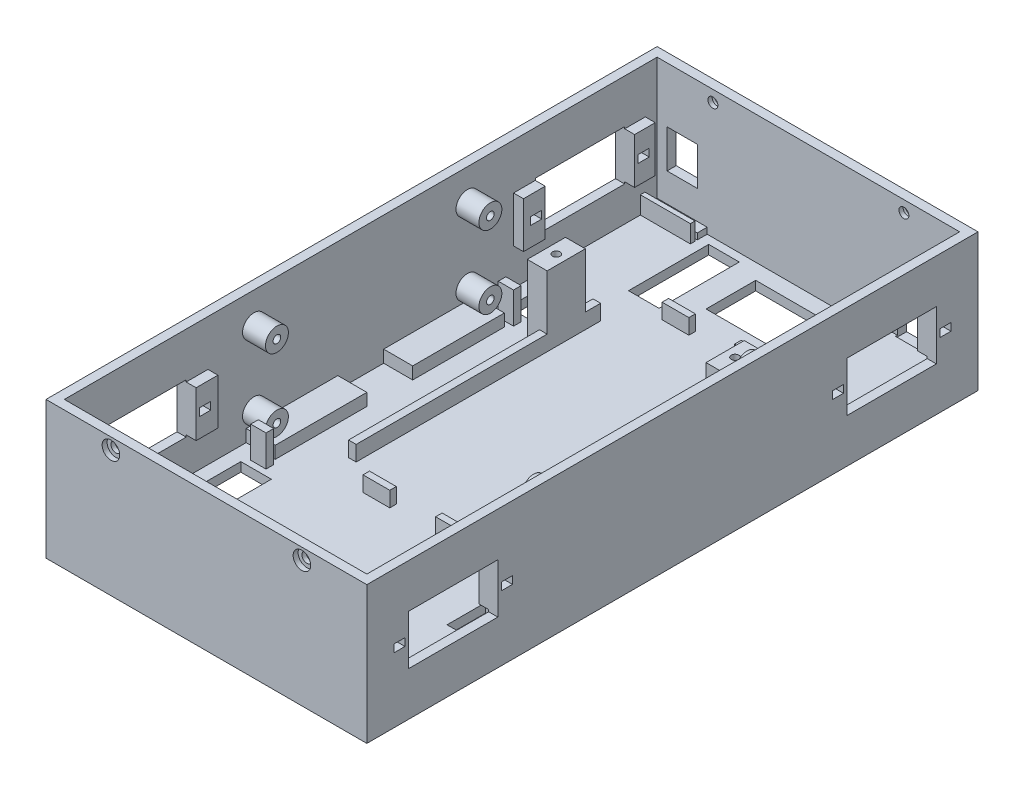
SolidWorks part; units mm, degrees
ref_plane "Front Plane" through (0, 0, 0) normal (0, 0, 1) x (1, 0, 0)
ref_plane "Top Plane" through (0, 0, 0) normal (0, 1, 0) x (1, 0, 0)
ref_plane "Right Plane" through (0, 0, 0) normal (1, 0, 0) x (0, 0, -1)
sketch "Sketch1" plane through (0, 0, 0) normal (0, 0, 1) x (1, 0, 0)
  line L1 (-42, 0) -> (42, 0)
  line L2 (-42, 0) -> (-42, 36)
  line L3 (-42, 36) -> (42, 36)
  line L4 (42, 0) -> (42, 36)
extrude "Boss-Extrude1" add sketch "Sketch1" along normal blind 160 from offset 80 offset against normal yes
sketch "Sketch2" plane through (0, 0, 0) normal (0, 0, 1) x (1, 0, 0)
  line L1 (-39.6, 2.4) -> (39.6, 2.4)
  line L2 (-39.6, 2.4) -> (-39.6, 41)
  line L3 (-39.6, 41) -> (39.6, 41)
  line L4 (39.6, 2.4) -> (39.6, 41)
extrude "Boss-Extrude2" add sketch "Sketch2" along normal blind 155.2 from offset 77.6 separate body offset against normal yes
combine bodies "Combine1" operation type subtract main body 101 bodies to subtract 102
sketch "Sketch3" plane through (0, 0, 0) normal (0, 0, 1) x (1, 0, 0)
  line L1 (-39.6, 12) -> (-37, 12)
  line L2 (-39.6, 12) -> (-39.6, 24)
  line L3 (-39.6, 24) -> (-37, 24)
  line L4 (-37, 12) -> (-37, 24)
extrude "Boss-Extrude3" add sketch "Sketch3" along normal blind 34.5 from offset 74.5 offset against normal yes
sketch "Sketch4" plane through (0, 0, 0) normal (0, 0, 1) x (1, 0, 0)
  line L1 (-43, 11.5) -> (-35.2, 11.5)
  line L2 (-43, 11.5) -> (-43, 24.5)
  line L3 (-43, 24.5) -> (-35.2, 24.5)
  line L4 (-35.2, 11.5) -> (-35.2, 24.5)
extrude "Boss-Extrude4" add sketch "Sketch4" along normal blind 23.4 from offset 69.1 separate body offset against normal yes
combine bodies "Combine2" operation type subtract main body 104 bodies to subtract 105
sketch "Sketch5" plane through (0, 0, 0) normal (0, 0, 1) x (1, 0, 0)
  line L1 (-43, 17) -> (-35.2, 17)
  line L2 (-43, 17) -> (-43, 19)
  line L3 (-43, 19) -> (-35.2, 19)
  line L4 (-35.2, 17) -> (-35.2, 19)
extrude "Boss-Extrude5" add sketch "Sketch5" along normal blind 2.9 from offset 72.925 separate body offset against normal yes
combine bodies "Combine3" operation type subtract main body 106 bodies to subtract 107
sketch "Sketch6" plane through (0, 0, 0) normal (0, 0, 1) x (1, 0, 0)
  line L1 (-43, 17) -> (-35.2, 17)
  line L2 (-43, 17) -> (-43, 19)
  line L3 (-43, 19) -> (-35.2, 19)
  line L4 (-35.2, 17) -> (-35.2, 19)
extrude "Boss-Extrude6" add sketch "Sketch6" along normal blind 2.9 from offset 44.775 separate body offset against normal yes
combine bodies "Combine4" operation type subtract main body 108 bodies to subtract 109
sketch "Sketch7" plane through (0, 0, 0) normal (0, 0, 1) x (1, 0, 0)
  line L1 (-36, -1) -> (-28, -1)
  line L2 (-36, -1) -> (-36, 3.4)
  line L3 (-36, 3.4) -> (-28, 3.4)
  line L4 (-28, -1) -> (-28, 3.4)
extrude "Boss-Extrude7" add sketch "Sketch7" along normal blind 10 from offset 45 separate body offset against normal yes
combine bodies "Combine5" operation type subtract main body 110 bodies to subtract 111
sketch "Sketch8" plane through (0, 0, 0) normal (0, 0, 1) x (1, 0, 0)
  line L1 (-39.6, 12) -> (-37, 12)
  line L2 (-39.6, 12) -> (-39.6, 24)
  line L3 (-39.6, 24) -> (-37, 24)
  line L4 (-37, 12) -> (-37, 24)
extrude "Boss-Extrude8" add sketch "Sketch8" along normal blind 34.5 from offset 40
sketch "Sketch9" plane through (0, 0, 0) normal (0, 0, 1) x (1, 0, 0)
  line L1 (-43, 11.5) -> (-35.2, 11.5)
  line L2 (-43, 11.5) -> (-43, 24.5)
  line L3 (-43, 24.5) -> (-35.2, 24.5)
  line L4 (-35.2, 11.5) -> (-35.2, 24.5)
extrude "Boss-Extrude9" add sketch "Sketch9" along normal blind 23.4 from offset 45.7 separate body
combine bodies "Combine6" operation type subtract main body 113 bodies to subtract 114
sketch "Sketch10" plane through (0, 0, 0) normal (0, 0, 1) x (1, 0, 0)
  line L1 (-43, 17) -> (-35.2, 17)
  line L2 (-43, 17) -> (-43, 19)
  line L3 (-43, 19) -> (-35.2, 19)
  line L4 (-35.2, 17) -> (-35.2, 19)
extrude "Boss-Extrude10" add sketch "Sketch10" along normal blind 2.9 from offset 41.875 separate body
combine bodies "Combine7" operation type subtract main body 115 bodies to subtract 116
sketch "Sketch11" plane through (0, 0, 0) normal (0, 0, 1) x (1, 0, 0)
  line L1 (-43, 17) -> (-35.2, 17)
  line L2 (-43, 17) -> (-43, 19)
  line L3 (-43, 19) -> (-35.2, 19)
  line L4 (-35.2, 17) -> (-35.2, 19)
extrude "Boss-Extrude11" add sketch "Sketch11" along normal blind 2.9 from offset 70.025 separate body
combine bodies "Combine8" operation type subtract main body 117 bodies to subtract 118
sketch "Sketch12" plane through (0, 0, 0) normal (0, 0, 1) x (1, 0, 0)
  line L1 (-36, -1) -> (-28, -1)
  line L2 (-36, -1) -> (-36, 3.4)
  line L3 (-36, 3.4) -> (-28, 3.4)
  line L4 (-28, -1) -> (-28, 3.4)
extrude "Boss-Extrude12" add sketch "Sketch12" along normal blind 10 from offset 35 separate body
combine bodies "Combine9" operation type subtract main body 119 bodies to subtract 120
sketch "Sketch13" plane through (0, 0, 0) normal (1, 0, 0) x (0, 0, -1)
  circle A0 centre (27.94, 8.775) radius 3
extrude "Boss-Extrude13" add sketch "Sketch13" along normal blind 6 from offset 39.6 offset against normal yes
sketch "Sketch14" plane through (0, 0, 0) normal (1, 0, 0) x (0, 0, -1)
  circle A0 centre (27.94, 8.775) radius 1
extrude "Boss-Extrude14" add sketch "Sketch14" along normal blind 7.4 from offset 40.4 separate body offset against normal yes
combine bodies "Combine10" operation type subtract main body 122 bodies to subtract 123
sketch "Sketch15" plane through (0, 0, 0) normal (1, 0, 0) x (0, 0, -1)
  circle A0 centre (27.94, 27.825) radius 3
extrude "Boss-Extrude15" add sketch "Sketch15" along normal blind 6 from offset 39.6 offset against normal yes
sketch "Sketch16" plane through (0, 0, 0) normal (1, 0, 0) x (0, 0, -1)
  circle A0 centre (27.94, 27.825) radius 1
extrude "Boss-Extrude16" add sketch "Sketch16" along normal blind 7.4 from offset 40.4 separate body offset against normal yes
combine bodies "Combine11" operation type subtract main body 125 bodies to subtract 126
sketch "Sketch17" plane through (0, 0, 0) normal (1, 0, 0) x (0, 0, -1)
  circle A0 centre (-27.94, 8.775) radius 3
extrude "Boss-Extrude17" add sketch "Sketch17" along normal blind 6 from offset 39.6 offset against normal yes
sketch "Sketch18" plane through (0, 0, 0) normal (1, 0, 0) x (0, 0, -1)
  circle A0 centre (-27.94, 8.775) radius 1
extrude "Boss-Extrude18" add sketch "Sketch18" along normal blind 7.4 from offset 40.4 separate body offset against normal yes
combine bodies "Combine12" operation type subtract main body 128 bodies to subtract 129
sketch "Sketch19" plane through (0, 0, 0) normal (1, 0, 0) x (0, 0, -1)
  circle A0 centre (-27.94, 27.825) radius 3
extrude "Boss-Extrude19" add sketch "Sketch19" along normal blind 6 from offset 39.6 offset against normal yes
sketch "Sketch20" plane through (0, 0, 0) normal (1, 0, 0) x (0, 0, -1)
  circle A0 centre (-27.94, 27.825) radius 1
extrude "Boss-Extrude20" add sketch "Sketch20" along normal blind 7.4 from offset 40.4 separate body offset against normal yes
combine bodies "Combine13" operation type subtract main body 131 bodies to subtract 132
sketch "Sketch21" plane through (0, 0, 0) normal (0, 0, 1) x (1, 0, 0)
  line L1 (-39.6, 2.4) -> (-32, 2.4)
  line L2 (-39.6, 2.4) -> (-39.6, 5.6)
  line L3 (-39.6, 5.6) -> (-32, 5.6)
  line L4 (-32, 2.4) -> (-32, 5.6)
extrude "Boss-Extrude21" add sketch "Sketch21" along normal blind 24 from offset 30 offset against normal yes
sketch "Sketch22" plane through (0, 0, 0) normal (0, 0, 1) x (1, 0, 0)
  line L1 (-39.6, 2.4) -> (-32, 2.4)
  line L2 (-39.6, 2.4) -> (-39.6, 5.6)
  line L3 (-39.6, 5.6) -> (-32, 5.6)
  line L4 (-32, 2.4) -> (-32, 5.6)
extrude "Boss-Extrude22" add sketch "Sketch22" along normal blind 24 from offset 6
sketch "Sketch23" plane through (0, 0, 0) normal (0, 0, 1) x (1, 0, 0)
  line L1 (-35, 2.4) -> (-31, 2.4)
  line L2 (-35, 2.4) -> (-35, 10.6)
  line L3 (-35, 10.6) -> (-31, 10.6)
  line L4 (-31, 2.4) -> (-31, 10.6)
extrude "Boss-Extrude23" add sketch "Sketch23" along normal blind 2 from offset 31.4
sketch "Sketch24" plane through (0, 0, 0) normal (0, 0, 1) x (1, 0, 0)
  line L1 (-35, 2.4) -> (-31, 2.4)
  line L2 (-35, 2.4) -> (-35, 10.6)
  line L3 (-35, 10.6) -> (-31, 10.6)
  line L4 (-31, 2.4) -> (-31, 10.6)
extrude "Boss-Extrude24" add sketch "Sketch24" along normal blind 2 from offset 33.4 offset against normal yes
sketch "Sketch25" plane through (0, 0, 0) normal (0, 0, 1) x (1, 0, 0)
  line L1 (-22.8, 2.4) -> (-20.8, 2.4)
  line L2 (-22.8, 2.4) -> (-22.8, 6.4)
  line L3 (-22.8, 6.4) -> (-20.8, 6.4)
  line L4 (-20.8, 2.4) -> (-20.8, 6.4)
extrude "Boss-Extrude25" add sketch "Sketch25" along normal blind 64 from offset 44 offset against normal yes
sketch "Sketch26" plane through (0, 0, 0) normal (0, 0, 1) x (1, 0, 0)
  line L1 (-26, 2.4) -> (-20.8, 2.4)
  line L2 (-26, 2.4) -> (-26, 20.75)
  line L3 (-26, 20.75) -> (-20.8, 20.75)
  line L4 (-20.8, 2.4) -> (-20.8, 20.75)
extrude "Boss-Extrude26" add sketch "Sketch26" along normal blind 10 from offset 40 offset against normal yes
sketch "Sketch27" plane through (0, 0, 0) normal (0, 1, 0) x (1, 0, 0)
  circle A0 centre (-23.4, 35) radius 1
extrude "Boss-Extrude27" add sketch "Sketch27" along normal blind 13.75 from offset 8 separate body
combine bodies "Combine14" operation type subtract main body 139 bodies to subtract 140
sketch "Sketch28" plane through (0, 0, 0) normal (0, 0, 1) x (1, 0, 0)
  line L1 (-24, -1) -> (-16, -1)
  line L2 (-24, -1) -> (-24, 3.4)
  line L3 (-24, 3.4) -> (-16, 3.4)
  line L4 (-16, -1) -> (-16, 3.4)
extrude "Boss-Extrude28" add sketch "Sketch28" along normal blind 21 from offset 54.5 separate body
combine bodies "Combine15" operation type subtract main body 141 bodies to subtract 142
sketch "Sketch29" plane through (0, 0, 0) normal (0, 0, 1) x (1, 0, 0)
  line L1 (37, 12) -> (39.6, 12)
  line L2 (37, 12) -> (37, 24)
  line L3 (37, 24) -> (39.6, 24)
  line L4 (39.6, 12) -> (39.6, 24)
extrude "Boss-Extrude29" add sketch "Sketch29" along normal blind 34.5 from offset 74.5 offset against normal yes
sketch "Sketch30" plane through (0, 0, 0) normal (0, 0, 1) x (1, 0, 0)
  line L1 (35.2, 11.5) -> (43, 11.5)
  line L2 (35.2, 11.5) -> (35.2, 24.5)
  line L3 (35.2, 24.5) -> (43, 24.5)
  line L4 (43, 11.5) -> (43, 24.5)
extrude "Boss-Extrude30" add sketch "Sketch30" along normal blind 23.4 from offset 69.1 separate body offset against normal yes
combine bodies "Combine16" operation type subtract main body 144 bodies to subtract 145
sketch "Sketch31" plane through (0, 0, 0) normal (0, 0, 1) x (1, 0, 0)
  line L1 (35.2, 17) -> (43, 17)
  line L2 (35.2, 17) -> (35.2, 19)
  line L3 (35.2, 19) -> (43, 19)
  line L4 (43, 17) -> (43, 19)
extrude "Boss-Extrude31" add sketch "Sketch31" along normal blind 2.9 from offset 72.925 separate body offset against normal yes
combine bodies "Combine17" operation type subtract main body 146 bodies to subtract 147
sketch "Sketch32" plane through (0, 0, 0) normal (0, 0, 1) x (1, 0, 0)
  line L1 (35.2, 17) -> (43, 17)
  line L2 (35.2, 17) -> (35.2, 19)
  line L3 (35.2, 19) -> (43, 19)
  line L4 (43, 17) -> (43, 19)
extrude "Boss-Extrude32" add sketch "Sketch32" along normal blind 2.9 from offset 44.775 separate body offset against normal yes
combine bodies "Combine18" operation type subtract main body 148 bodies to subtract 149
sketch "Sketch33" plane through (0, 0, 0) normal (0, 0, 1) x (1, 0, 0)
  line L1 (28, -1) -> (36, -1)
  line L2 (28, -1) -> (28, 3.4)
  line L3 (28, 3.4) -> (36, 3.4)
  line L4 (36, -1) -> (36, 3.4)
extrude "Boss-Extrude33" add sketch "Sketch33" along normal blind 10 from offset 45 separate body offset against normal yes
combine bodies "Combine19" operation type subtract main body 150 bodies to subtract 151
sketch "Sketch34" plane through (0, 0, 0) normal (0, 0, 1) x (1, 0, 0)
  line L1 (37, 12) -> (39.6, 12)
  line L2 (37, 12) -> (37, 24)
  line L3 (37, 24) -> (39.6, 24)
  line L4 (39.6, 12) -> (39.6, 24)
extrude "Boss-Extrude34" add sketch "Sketch34" along normal blind 34.5 from offset 40
sketch "Sketch35" plane through (0, 0, 0) normal (0, 0, 1) x (1, 0, 0)
  line L1 (35.2, 11.5) -> (43, 11.5)
  line L2 (35.2, 11.5) -> (35.2, 24.5)
  line L3 (35.2, 24.5) -> (43, 24.5)
  line L4 (43, 11.5) -> (43, 24.5)
extrude "Boss-Extrude35" add sketch "Sketch35" along normal blind 23.4 from offset 45.7 separate body
combine bodies "Combine20" operation type subtract main body 153 bodies to subtract 154
sketch "Sketch36" plane through (0, 0, 0) normal (0, 0, 1) x (1, 0, 0)
  line L1 (35.2, 17) -> (43, 17)
  line L2 (35.2, 17) -> (35.2, 19)
  line L3 (35.2, 19) -> (43, 19)
  line L4 (43, 17) -> (43, 19)
extrude "Boss-Extrude36" add sketch "Sketch36" along normal blind 2.9 from offset 41.875 separate body
combine bodies "Combine21" operation type subtract main body 155 bodies to subtract 156
sketch "Sketch37" plane through (0, 0, 0) normal (0, 0, 1) x (1, 0, 0)
  line L1 (35.2, 17) -> (43, 17)
  line L2 (35.2, 17) -> (35.2, 19)
  line L3 (35.2, 19) -> (43, 19)
  line L4 (43, 17) -> (43, 19)
extrude "Boss-Extrude37" add sketch "Sketch37" along normal blind 2.9 from offset 70.025 separate body
combine bodies "Combine22" operation type subtract main body 157 bodies to subtract 158
sketch "Sketch38" plane through (0, 0, 0) normal (0, 0, 1) x (1, 0, 0)
  line L1 (28, -1) -> (36, -1)
  line L2 (28, -1) -> (28, 3.4)
  line L3 (28, 3.4) -> (36, 3.4)
  line L4 (36, -1) -> (36, 3.4)
extrude "Boss-Extrude38" add sketch "Sketch38" along normal blind 10 from offset 35 separate body
combine bodies "Combine23" operation type subtract main body 159 bodies to subtract 160
sketch "Sketch39" plane through (0, 0, 0) normal (1, 0, 0) x (0, 0, -1)
  circle A0 centre (27.94, 8.775) radius 3
extrude "Boss-Extrude39" add sketch "Sketch39" along normal blind 6 from offset 33.6
sketch "Sketch40" plane through (0, 0, 0) normal (1, 0, 0) x (0, 0, -1)
  circle A0 centre (27.94, 8.775) radius 1
extrude "Boss-Extrude40" add sketch "Sketch40" along normal blind 7.4 from offset 33 separate body
combine bodies "Combine24" operation type subtract main body 162 bodies to subtract 163
sketch "Sketch41" plane through (0, 0, 0) normal (1, 0, 0) x (0, 0, -1)
  circle A0 centre (27.94, 27.825) radius 3
extrude "Boss-Extrude41" add sketch "Sketch41" along normal blind 6 from offset 33.6
sketch "Sketch42" plane through (0, 0, 0) normal (1, 0, 0) x (0, 0, -1)
  circle A0 centre (27.94, 27.825) radius 1
extrude "Boss-Extrude42" add sketch "Sketch42" along normal blind 7.4 from offset 33 separate body
combine bodies "Combine25" operation type subtract main body 165 bodies to subtract 166
sketch "Sketch43" plane through (0, 0, 0) normal (1, 0, 0) x (0, 0, -1)
  circle A0 centre (-27.94, 8.775) radius 3
extrude "Boss-Extrude43" add sketch "Sketch43" along normal blind 6 from offset 33.6
sketch "Sketch44" plane through (0, 0, 0) normal (1, 0, 0) x (0, 0, -1)
  circle A0 centre (-27.94, 8.775) radius 1
extrude "Boss-Extrude44" add sketch "Sketch44" along normal blind 7.4 from offset 33 separate body
combine bodies "Combine26" operation type subtract main body 168 bodies to subtract 169
sketch "Sketch45" plane through (0, 0, 0) normal (1, 0, 0) x (0, 0, -1)
  circle A0 centre (-27.94, 27.825) radius 3
extrude "Boss-Extrude45" add sketch "Sketch45" along normal blind 6 from offset 33.6
sketch "Sketch46" plane through (0, 0, 0) normal (1, 0, 0) x (0, 0, -1)
  circle A0 centre (-27.94, 27.825) radius 1
extrude "Boss-Extrude46" add sketch "Sketch46" along normal blind 7.4 from offset 33 separate body
combine bodies "Combine27" operation type subtract main body 171 bodies to subtract 172
sketch "Sketch47" plane through (0, 0, 0) normal (0, 0, 1) x (1, 0, 0)
  line L1 (32, 2.4) -> (39.6, 2.4)
  line L2 (32, 2.4) -> (32, 5.6)
  line L3 (32, 5.6) -> (39.6, 5.6)
  line L4 (39.6, 2.4) -> (39.6, 5.6)
extrude "Boss-Extrude47" add sketch "Sketch47" along normal blind 24 from offset 30 offset against normal yes
sketch "Sketch48" plane through (0, 0, 0) normal (0, 0, 1) x (1, 0, 0)
  line L1 (32, 2.4) -> (39.6, 2.4)
  line L2 (32, 2.4) -> (32, 5.6)
  line L3 (32, 5.6) -> (39.6, 5.6)
  line L4 (39.6, 2.4) -> (39.6, 5.6)
extrude "Boss-Extrude48" add sketch "Sketch48" along normal blind 24 from offset 6
sketch "Sketch49" plane through (0, 0, 0) normal (0, 0, 1) x (1, 0, 0)
  line L1 (31, 2.4) -> (35, 2.4)
  line L2 (31, 2.4) -> (31, 10.6)
  line L3 (31, 10.6) -> (35, 10.6)
  line L4 (35, 2.4) -> (35, 10.6)
extrude "Boss-Extrude49" add sketch "Sketch49" along normal blind 2 from offset 31.4
sketch "Sketch50" plane through (0, 0, 0) normal (0, 0, 1) x (1, 0, 0)
  line L1 (31, 2.4) -> (35, 2.4)
  line L2 (31, 2.4) -> (31, 10.6)
  line L3 (31, 10.6) -> (35, 10.6)
  line L4 (35, 2.4) -> (35, 10.6)
extrude "Boss-Extrude50" add sketch "Sketch50" along normal blind 2 from offset 33.4 offset against normal yes
sketch "Sketch51" plane through (0, 0, 0) normal (0, 0, 1) x (1, 0, 0)
  line L1 (20.8, 2.4) -> (22.8, 2.4)
  line L2 (20.8, 2.4) -> (20.8, 6.4)
  line L3 (20.8, 6.4) -> (22.8, 6.4)
  line L4 (22.8, 2.4) -> (22.8, 6.4)
extrude "Boss-Extrude51" add sketch "Sketch51" along normal blind 64 from offset 44 offset against normal yes
sketch "Sketch52" plane through (0, 0, 0) normal (0, 0, 1) x (1, 0, 0)
  line L1 (20.8, 2.4) -> (26, 2.4)
  line L2 (20.8, 2.4) -> (20.8, 20.75)
  line L3 (20.8, 20.75) -> (26, 20.75)
  line L4 (26, 2.4) -> (26, 20.75)
extrude "Boss-Extrude52" add sketch "Sketch52" along normal blind 10 from offset 40 offset against normal yes
sketch "Sketch53" plane through (0, 0, 0) normal (0, 1, 0) x (1, 0, 0)
  circle A0 centre (23.4, 35) radius 1
extrude "Boss-Extrude53" add sketch "Sketch53" along normal blind 13.75 from offset 8 separate body
combine bodies "Combine28" operation type subtract main body 179 bodies to subtract 180
sketch "Sketch54" plane through (0, 0, 0) normal (0, 0, 1) x (1, 0, 0)
  line L1 (16, -1) -> (24, -1)
  line L2 (16, -1) -> (16, 3.4)
  line L3 (16, 3.4) -> (24, 3.4)
  line L4 (24, -1) -> (24, 3.4)
extrude "Boss-Extrude54" add sketch "Sketch54" along normal blind 21 from offset 54.5 separate body
combine bodies "Combine29" operation type subtract main body 181 bodies to subtract 182
sketch "Sketch55" plane through (0, 0, 0) normal (0, 0, 1) x (1, 0, 0)
  line L1 (-13, 2.4) -> (-6, 2.4)
  line L2 (-13, 2.4) -> (-13, 6.4)
  line L3 (-13, 6.4) -> (-6, 6.4)
  line L4 (-6, 2.4) -> (-6, 6.4)
extrude "Boss-Extrude55" add sketch "Sketch55" along normal blind 1.7 from offset 54 offset against normal yes
sketch "Sketch56" plane through (0, 0, 0) normal (0, 0, 1) x (1, 0, 0)
  line L1 (6, 2.4) -> (13, 2.4)
  line L2 (6, 2.4) -> (6, 6.4)
  line L3 (6, 6.4) -> (13, 6.4)
  line L4 (13, 2.4) -> (13, 6.4)
extrude "Boss-Extrude56" add sketch "Sketch56" along normal blind 1.7 from offset 54 offset against normal yes
sketch "Sketch57" plane through (0, 0, 0) normal (0, 0, 1) x (1, 0, 0)
  line L1 (-13, 2.4) -> (-6, 2.4)
  line L2 (-13, 2.4) -> (-13, 6.4)
  line L3 (-13, 6.4) -> (-6, 6.4)
  line L4 (-6, 2.4) -> (-6, 6.4)
extrude "Boss-Extrude57" add sketch "Sketch57" along normal blind 1.7 from offset 24.3
sketch "Sketch58" plane through (0, 0, 0) normal (0, 0, 1) x (1, 0, 0)
  line L1 (6, 2.4) -> (13, 2.4)
  line L2 (6, 2.4) -> (6, 6.4)
  line L3 (6, 6.4) -> (13, 6.4)
  line L4 (13, 2.4) -> (13, 6.4)
extrude "Boss-Extrude58" add sketch "Sketch58" along normal blind 1.7 from offset 24.3
sketch "Sketch59" plane through (0, 0, 0) normal (0, 0, 1) x (1, 0, 0)
  line L1 (-24, -1) -> (-16, -1)
  line L2 (-24, -1) -> (-24, 3.4)
  line L3 (-24, 3.4) -> (-16, 3.4)
  line L4 (-16, -1) -> (-16, 3.4)
extrude "Boss-Extrude59" add sketch "Sketch59" along normal blind 21 from offset 75.5 separate body offset against normal yes
combine bodies "Combine30" operation type subtract main body 187 bodies to subtract 188
sketch "Sketch60" plane through (0, 0, 0) normal (0, 0, 1) x (1, 0, 0)
  line L1 (-9.7, -1) -> (9.7, -1)
  line L2 (-9.7, -1) -> (-9.7, 3.4)
  line L3 (-9.7, 3.4) -> (9.7, 3.4)
  line L4 (9.7, -1) -> (9.7, 3.4)
extrude "Boss-Extrude60" add sketch "Sketch60" along normal blind 13 from offset 73.5 separate body offset against normal yes
combine bodies "Combine31" operation type subtract main body 189 bodies to subtract 190
sketch "Sketch61" plane through (0, 0, 0) normal (0, 0, 1) x (1, 0, 0)
  line L1 (21.3, 2.4) -> (39.3, 2.4)
  line L2 (21.3, 2.4) -> (21.3, 4.4)
  line L3 (21.3, 4.4) -> (39.3, 4.4)
  line L4 (39.3, 2.4) -> (39.3, 4.4)
extrude "Boss-Extrude61" add sketch "Sketch61" along normal blind 31 from offset 77.6 offset against normal yes
sketch "Sketch62" plane through (0, 0, 0) normal (0, 0, 1) x (1, 0, 0)
  line L1 (19.5, 2.4) -> (21.3, 2.4)
  line L2 (19.5, 2.4) -> (19.5, 7.4)
  line L3 (19.5, 7.4) -> (21.3, 7.4)
  line L4 (21.3, 2.4) -> (21.3, 7.4)
extrude "Boss-Extrude62" add sketch "Sketch62" along normal blind 22 from offset 75 offset against normal yes
sketch "Sketch63" plane through (0, 0, 0) normal (0, 0, 1) x (1, 0, 0)
  line L1 (21.3, 2.4) -> (39.6, 2.4)
  line L2 (21.3, 2.4) -> (21.3, 7.4)
  line L3 (21.3, 7.4) -> (39.6, 7.4)
  line L4 (39.6, 2.4) -> (39.6, 7.4)
extrude "Boss-Extrude63" add sketch "Sketch63" along normal blind 1.2 from offset 46.4 offset against normal yes
sketch "Sketch64" plane through (0, 0, 0) normal (0, 0, 1) x (1, 0, 0)
  line L1 (23.3, 4) -> (37.3, 4)
  line L2 (23.3, 4) -> (23.3, 11.5)
  line L3 (23.3, 11.5) -> (37.3, 11.5)
  line L4 (37.3, 4) -> (37.3, 11.5)
extrude "Boss-Extrude64" add sketch "Sketch64" along normal blind 3.9 from offset 81 separate body offset against normal yes
combine bodies "Combine32" operation type subtract main body 194 bodies to subtract 195
sketch "Sketch65" plane through (0, 0, 0) normal (0, 0, 1) x (1, 0, 0)
  line L1 (-39.6, 2.4) -> (-26.5, 2.4)
  line L2 (-39.6, 2.4) -> (-39.6, 4)
  line L3 (-39.6, 4) -> (-26.5, 4)
  line L4 (-26.5, 2.4) -> (-26.5, 4)
extrude "Boss-Extrude65" add sketch "Sketch65" along normal blind 2.6 from offset 77.6 offset against normal yes
sketch "Sketch66" plane through (0, 0, 0) normal (0, 0, 1) x (1, 0, 0)
  line L1 (-39.6, 2.4) -> (-26.5, 2.4)
  line L2 (-39.6, 2.4) -> (-39.6, 7)
  line L3 (-39.6, 7) -> (-26.5, 7)
  line L4 (-26.5, 2.4) -> (-26.5, 7)
extrude "Boss-Extrude66" add sketch "Sketch66" along normal blind 1.2 from offset 74.4 offset against normal yes
sketch "Sketch67" plane through (0, 0, 0) normal (0, 0, 1) x (1, 0, 0)
  line L1 (-37, 11.5) -> (-29, 11.5)
  line L2 (-37, 11.5) -> (-37, 21.5)
  line L3 (-37, 21.5) -> (-29, 21.5)
  line L4 (-29, 11.5) -> (-29, 21.5)
extrude "Boss-Extrude67" add sketch "Sketch67" along normal blind 3.9 from offset 81 separate body offset against normal yes
combine bodies "Combine33" operation type subtract main body 198 bodies to subtract 199
sketch "Sketch68" plane through (0, 0, 0) normal (0, 0, 1) x (1, 0, 0)
  circle A0 centre (-25, 33) radius 1.3
extrude "Boss-Extrude68" add sketch "Sketch68" along normal blind 4.4 from offset 81 separate body offset against normal yes
combine bodies "Combine34" operation type subtract main body 200 bodies to subtract 201
sketch "Sketch69" plane through (0, 0, 0) normal (0, 0, 1) x (1, 0, 0)
  circle A0 centre (-25, 33) radius 2.3
extrude "Boss-Extrude69" add sketch "Sketch69" along normal blind 2.3 from offset 81 separate body offset against normal yes
combine bodies "Combine35" operation type subtract main body 202 bodies to subtract 203
sketch "Sketch70" plane through (0, 0, 0) normal (0, 0, 1) x (1, 0, 0)
  circle A0 centre (25, 33) radius 1.3
extrude "Boss-Extrude70" add sketch "Sketch70" along normal blind 4.4 from offset 81 separate body offset against normal yes
combine bodies "Combine36" operation type subtract main body 204 bodies to subtract 205
sketch "Sketch71" plane through (0, 0, 0) normal (0, 0, 1) x (1, 0, 0)
  circle A0 centre (25, 33) radius 2.3
extrude "Boss-Extrude71" add sketch "Sketch71" along normal blind 2.3 from offset 81 separate body offset against normal yes
combine bodies "Combine37" operation type subtract main body 206 bodies to subtract 207
sketch "Sketch72" plane through (0, 0, 0) normal (0, 0, 1) x (1, 0, 0)
  circle A0 centre (-25, 33) radius 1.3
extrude "Boss-Extrude72" add sketch "Sketch72" along normal blind 4.4 from offset 76.6 separate body
combine bodies "Combine38" operation type subtract main body 208 bodies to subtract 209
sketch "Sketch73" plane through (0, 0, 0) normal (0, 0, 1) x (1, 0, 0)
  circle A0 centre (-25, 33) radius 2.3
extrude "Boss-Extrude73" add sketch "Sketch73" along normal blind 2.3 from offset 78.7 separate body
combine bodies "Combine39" operation type subtract main body 210 bodies to subtract 211
sketch "Sketch74" plane through (0, 0, 0) normal (0, 0, 1) x (1, 0, 0)
  circle A0 centre (25, 33) radius 1.3
extrude "Boss-Extrude74" add sketch "Sketch74" along normal blind 4.4 from offset 76.6 separate body
combine bodies "Combine40" operation type subtract main body 212 bodies to subtract 213
sketch "Sketch75" plane through (0, 0, 0) normal (0, 0, 1) x (1, 0, 0)
  circle A0 centre (25, 33) radius 2.3
extrude "Boss-Extrude75" add sketch "Sketch75" along normal blind 2.3 from offset 78.7 separate body
combine bodies "Combine41" operation type subtract main body 214 bodies to subtract 215
